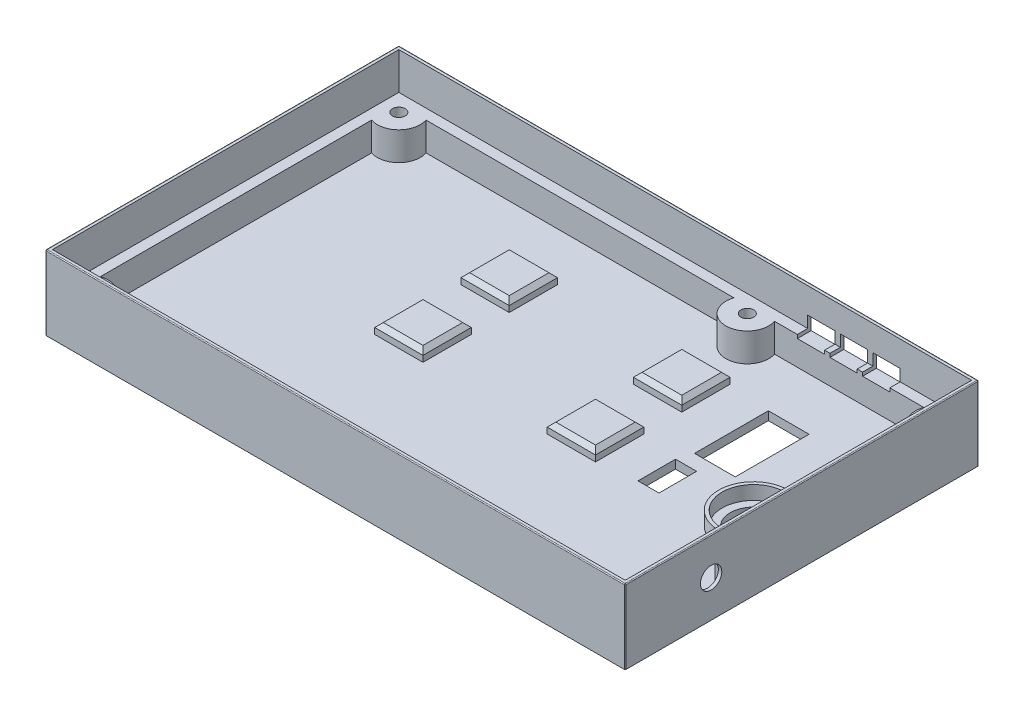
SolidWorks part; units mm, degrees
ref_plane "Front Plane" through (0, 0, 0) normal (0, 0, 1) x (1, 0, 0)
ref_plane "Top Plane" through (0, 0, 0) normal (0, 1, 0) x (1, 0, 0)
ref_plane "Right Plane" through (0, 0, 0) normal (1, 0, 0) x (0, 0, -1)
sketch "BaseSketch1" plane through (0, 0, 0) normal (0, 1, 0) x (1, 0, 0)
  line L1 (0, 0) -> (168, 0)
  line L2 (0, 0) -> (0, 102.4)
  line L3 (0, 102.4) -> (168, 102.4)
  line L4 (168, 0) -> (168, 102.4)
  line L5 (126.2, 83.3) -> (138, 83.3)
  line L6 (126.2, 83.3) -> (126.2, 61.9)
  line L7 (126.2, 61.9) -> (138, 61.9)
  line L8 (138, 83.3) -> (138, 61.9)
  line L9 (124.9, 46.8) -> (131, 46.8)
  line L10 (124.9, 46.8) -> (124.9, 57.7)
  line L11 (124.9, 57.7) -> (131, 57.7)
  line L12 (131, 46.8) -> (131, 57.7)
  circle A0 centre (57, 77.4) radius 2
  circle A1 centre (107, 77.4) radius 2
  circle A2 centre (57, 52.4) radius 2
  circle A3 centre (107, 52.4) radius 2
  circle A4 centre (6, 96.4) radius 1.85
  circle A5 centre (6, 6) radius 1.85
  circle A6 centre (162, 6) radius 1.85
  circle A7 centre (162, 96.4) radius 1.85
  circle A8 centre (107, 96.4) radius 1.85
  dimension "D16" = 3.7
  dimension "D7" = 4
  dimension "D1" = 102.4
  dimension "D2" = 168
  dimension "D3" = 50
  dimension "D4" = 25
  dimension "D6" = 25
  dimension "D8" = 21.4
  dimension "D9" = 11.8
  dimension "D10" = 40.5
  dimension "D12" = 6.1
  dimension "D13" = 10.9
  dimension "D15" = 55.6
  dimension "D17" = 6
  dimension "D18" = 6
  dimension "D19" = 6
  dimension "D20" = 6
  dimension "D5" = 57
  dimension "D11" = 41.8
  dimension "D14" = 43.1
  dimension "D21" = 107
extrude "BaseBoss-Extrude1" add sketch "BaseSketch1" along normal blind 2.5
sketch "Sketch2" plane through (0, 2.5, 0) normal (0, 1, 0) x (1, 0, 0)
  line L1 (0, 0) -> (168, 0)
  line L2 (0, 0) -> (0, 102.4)
  line L3 (0, 102.4) -> (168, 102.4)
  line L4 (168, 0) -> (168, 102.4)
  line L5 (4, 98.4) -> (164, 98.4)
  line L6 (4, 98.4) -> (4, 4)
  line L7 (4, 4) -> (164, 4)
  line L8 (164, 98.4) -> (164, 4)
  dimension "D1" = 4
  dimension "D2" = 4
  dimension "D3" = 4
  dimension "D4" = 4
extrude "WallBoss-Extrude2" add sketch "Sketch2" along normal blind 19
sketch "Sketch3" plane through (0, 2.5, 0) normal (0, 1, 0) x (1, 0, 0)
  line L1 (50, 84.4) -> (64, 84.4)
  line L2 (50, 84.4) -> (50, 70.4)
  line L3 (50, 70.4) -> (64, 70.4)
  line L4 (64, 84.4) -> (64, 70.4)
  line L5 (50, 84.4) -> (64, 70.4) construction
  line L6 (50, 70.4) -> (64, 84.4) construction
  line L7 (50, 59.4) -> (64, 59.4)
  line L8 (50, 59.4) -> (50, 45.4)
  line L9 (50, 45.4) -> (64, 45.4)
  line L10 (64, 59.4) -> (64, 45.4)
  line L11 (50, 59.4) -> (64, 45.4) construction
  line L12 (50, 45.4) -> (64, 59.4) construction
  line L13 (100, 84.4) -> (114, 84.4)
  line L14 (100, 84.4) -> (100, 70.4)
  line L15 (100, 70.4) -> (114, 70.4)
  line L16 (114, 84.4) -> (114, 70.4)
  line L17 (100, 84.4) -> (114, 70.4) construction
  line L18 (100, 70.4) -> (114, 84.4) construction
  line L19 (100, 59.4) -> (114, 59.4)
  line L20 (100, 59.4) -> (100, 45.4)
  line L21 (100, 45.4) -> (114, 45.4)
  line L22 (114, 59.4) -> (114, 45.4)
  line L23 (100, 59.4) -> (114, 45.4) construction
  line L24 (100, 45.4) -> (114, 59.4) construction
  point P0 (57, 77.4)
  point P6 (57, 52.4)
  point P12 (107, 77.4)
  point P18 (107, 52.4)
  dimension "D1" = 14
extrude "MountHoleBoss-Extrude3" add sketch "Sketch3" along normal blind 3
chamfer "MountHoleBossChamfer3" distance 1.25 angle 45 16 edges at (57, 5.5, -59.4) (107, 5.5, -59.4) (107, 5.5, -84.4) (57, 5.5, -84.4) (50, 5.5, -52.4) (100, 5.5, -52.4) (100, 5.5, -77.4) (50, 5.5, -77.4) (64, 5.5, -52.4) (114, 5.5, -52.4) (114, 5.5, -77.4) (64, 5.5, -77.4) (57, 5.5, -70.4) (57, 5.5, -45.4) (107, 5.5, -45.4) (107, 5.5, -70.4)
sketch "HDMI7MountHolesSketch8" plane through (0, 2.5, 0) normal (0, 1, 0) x (1, 0, 0)
  line L0 (164, 98.4) -> (4, 98.4) construction
  line L1 (4, 98.4) -> (4, 4) construction
  line L2 (4, 90.5243) -> (4, 98.4)
  line L3 (4, 98.4) -> (11.8757, 98.4)
  line L4 (164, 4) -> (164, 98.4) construction
  line L5 (4, 4) -> (164, 4) construction
  line L6 (4, 98.4) -> (4, 4) construction
  line L7 (4, 4) -> (164, 4) construction
  line L8 (156.1243, 98.4) -> (164, 98.4)
  line L9 (164, 98.4) -> (164, 90.5243)
  line L10 (156.1243, 4) -> (164, 4)
  line L11 (164, 4) -> (164, 11.8757)
  line L12 (11.8757, 4) -> (4, 4)
  line L13 (4, 4) -> (4, 11.8757)
  line L14 (101.1243, 98.4) -> (112.8757, 98.4)
  arc A0 (11.8757, 98.4) -> (4, 90.5243) centre (6, 96.4) cw
  circle A1 centre (6, 96.4) radius 1.85
  circle A2 centre (6, 96.4) radius 1.85 construction
  circle A3 centre (162, 96.4) radius 1.85
  circle A4 centre (162, 96.4) radius 1.85 construction
  arc A5 (164, 90.5243) -> (156.1243, 98.4) centre (162, 96.4) cw
  arc A6 (164, 11.8757) -> (156.1243, 4) centre (162, 6) ccw
  arc A7 (4, 11.8757) -> (11.8757, 4) centre (6, 6) cw
  circle A8 centre (162, 6) radius 1.85
  circle A9 centre (162, 6) radius 1.85 construction
  circle A10 centre (6, 6) radius 1.85
  circle A11 centre (6, 6) radius 1.85 construction
  arc A12 (101.1243, 98.4) -> (112.8757, 98.4) centre (107, 96.4) ccw
  circle A13 centre (107, 96.4) radius 1.85
  circle A14 centre (107, 96.4) radius 1.85 construction
extrude "HDMI7MountHolesBoss-Extrude4" add sketch "HDMI7MountHolesSketch8" along normal blind 8.25
sketch "DisplayButtonsSketch9" plane through (0, 0, -102.4) normal (0, 0, -1) x (-1, 0, 0)
  line L0 (-168, 21.5) -> (0, 21.5) construction
  line L1 (-146.3, 14.11) -> (-138.4, 14.11)
  line L2 (-146.3, 14.11) -> (-146.3, 9.71)
  line L3 (-146.3, 9.71) -> (-138.4, 9.71)
  line L4 (-138.4, 14.11) -> (-138.4, 9.71)
  line L5 (-136.85, 14.11) -> (-128.95, 14.11)
  line L6 (-136.85, 14.11) -> (-136.85, 9.71)
  line L7 (-136.85, 9.71) -> (-128.95, 9.71)
  line L8 (-128.95, 14.11) -> (-128.95, 9.71)
  line L9 (-127.4, 14.11) -> (-119.5, 14.11)
  line L10 (-127.4, 14.11) -> (-127.4, 9.71)
  line L11 (-127.4, 9.71) -> (-119.5, 9.71)
  line L12 (-119.5, 14.11) -> (-119.5, 9.71)
  line L13 (-168, 21.5) -> (-168, 0) construction
  dimension "D1" = 7.9
  dimension "D3" = 11.79
  dimension "D4" = 29.6
  dimension "D2" = 4.4
  dimension "D6" = 1.55
  dimension "D5" = 1.55
  dimension "D7" = 48.5
  dimension "D8" = 7.9
  dimension "D9" = 7.9
extrude "DisplayButtonsCut-Extrude1" cut sketch "DisplayButtonsSketch9" against normal up to next
sketch "AudioConnectorSketch10" plane through (168, 0, 0) normal (1, 0, 0) x (0, 0, -1)
  line L0 (0, 21.5) -> (102.4, 21.5) construction
  line L1 (0, 21.5) -> (0, 0) construction
  circle A0 centre (24.9, 10.7) radius 3.1
  dimension "D1" = 6.2
  dimension "D2" = 10.8
  dimension "D3" = 24.9
extrude "AudioConnectorCut-Extrude2" cut sketch "AudioConnectorSketch10" against normal up to next
sketch "M3BoreSketch11" plane through (0, 0, 0) normal (0, -1, 0) x (1, 0, 0)
  circle A0 centre (6, -6) radius 2.85
  circle A1 centre (162, -6) radius 2.85
  circle A2 centre (162, -96.4) radius 2.85
  circle A3 centre (6, -96.4) radius 2.85
  circle A4 centre (107, -96.4) radius 2.85
  dimension "D1" = 5.7
extrude "M3BoreCut-Extrude3" cut sketch "M3BoreSketch11" against normal blind 3
sketch "UpperThinWallSketch4" plane through (0, 21.5, 0) normal (0, 1, 0) x (1, 0, 0)
  line L1 (4, 98.4) -> (164, 98.4)
  line L2 (4, 98.4) -> (4, 4)
  line L3 (4, 4) -> (164, 4)
  line L4 (164, 98.4) -> (164, 4)
  line L6 (167, 1) -> (1, 1)
  line L7 (167, 1) -> (167, 101.4)
  line L8 (167, 101.4) -> (1, 101.4)
  line L9 (1, 1) -> (1, 101.4)
  dimension "D1" = 3
  dimension "D2" = 3
  dimension "D3" = 3
  dimension "D4" = 3
extrude "UpperThinWallCut-Extrude1" cut sketch "UpperThinWallSketch4" against normal blind 10.75
sketch "HDMI7AudioConnectorKnotchSketch5" plane through (0, 10.75, 0) normal (0, 1, 0) x (1, 0, 0)
  line L0 (164, 27.9996) -> (167, 27.9996) construction
  line L1 (164, 29.9996) -> (167, 29.9996)
  line L2 (164, 29.9996) -> (164, 19.8004)
  line L3 (164, 19.8004) -> (167, 19.8004)
  line L4 (167, 29.9996) -> (167, 19.8004)
  line L6 (167, 1) -> (167, 21.8004) construction
  line L7 (164, 11.8757) -> (164, 90.5243) construction
  line L8 (167, 21.8004) -> (164, 21.8004) construction
  dimension "D1" = 2
  dimension "D2" = 2
extrude "HDMI7AudioConnectorKnotchCut-Extrude2" cut sketch "HDMI7AudioConnectorKnotchSketch5" against normal blind 8.2
fillet "TopFillet1" radius 0.25 4 edges at (168, 21.5, -51.2) (84, 21.5, 0) (0, 21.5, -51.2) (84, 21.5, -102.4)
fillet "CornerFillet2" radius 0.25 8 edges at (0.0732, 21.4268, -0.0732) (0.0732, 21.4268, -102.3268) (167.9268, 21.4268, -0.0732) (0, 10.625, 0) (0, 10.625, -102.4) (168, 10.625, 0) (167.9268, 21.4268, -102.3268) (168, 10.625, -102.4)
sketch "SpeakerHoleSketch4" plane through (0, 2.5, 0) normal (0, 1, 0) x (1, 0, 0)
  line L0 (0.25, 102.4) -> (167.75, 102.4) construction
  line L1 (168, 102.15) -> (168, 0.25) construction
  circle A0 centre (153, 52.2) radius 6.75
  dimension "D1" = 13.5
  dimension "D2" = 50.2
  dimension "D3" = 15
extrude "SpeaerHoleCut-Extrude1" cut sketch "SpeakerHoleSketch4" against normal through all
sketch "SpeakerHolderSketch5" plane through (0, 2.5, 0) normal (0, 1, 0) x (1, 0, 0)
  line L2 (50, 59.4) -> (50, 45.4) construction
  line L3 (50, 45.4) -> (64, 45.4) construction
  circle A0 centre (153, 52.2) radius 9.1
  circle A1 centre (153, 52.2) radius 10.1
  dimension "D1" = 18.2
  dimension "D2" = 20.2
extrude "SpeakerHolderBoss-Extrude1" add sketch "SpeakerHolderSketch5" along normal blind 4
equation "\"HDMI7CaseWidth\"= 100mm + .4mm'Spec Add .4mm as width was slightly to tight"
equation "\"D1@BaseSketch1\" = \"HDMI7CaseWidth\" + \"HDMI7OuterCaseWallThickness\" * 2"
equation "\"HDMI7CaseLength\"= 165mm + 1mm'Spec Add 1mm as length did not fit"
equation "\"HDMI7CaseHeight\"= 21.5mm"
equation "\"HDMI7Height\"= 10.75mm'Spec"
equation "\"HDMI7MountingHoleOffset\"= 5mm'Spec"
equation "\"M3ScrewDiameter\"= 3mm + .5'Spec Add .5mm for easy screw insert"
equation "\"D2@BaseSketch1\"= \"HDMI7CaseLength\" + \"HDMI7OuterCaseWallThickness\" * 2"
equation "\"HDMI7BaseThickness\"= 2.5mm"
equation "\"HDMIMountHoleXDistance\"=50"
equation "\"D3@BaseSketch1\"=\"HDMIMountHoleXDistance\""
equation "\"HDMIMountHoleYDistance\"=25"
equation "\"D10@BaseSketch1\"=\"HDMI7HDMIConnectorDistanceFromTop\" + \"HDMI7OuterCaseWallThickness\" + \"HDMI7SpaceAroundAConnector\""
equation "\"D6@BaseSketch1\" = \"HDMI7MountingBracketOffsetFromTop\" + \"HDMI7OuterCaseWallThickness\""
equation "\"D15@BaseSketch1\"=\"HDMI7USBCConnectorDistanceFromTop\" + \"HDMI7OuterCaseWallThickness\" + \"HDMI7SpaceAroundAConnector\"*2"
equation "\"D1@BaseBoss-Extrude1\" = \"HDMI7BaseThickness\""
equation "\"D1@Sketch2\"=\"HDMI7OuterCaseWallThickness\" + \"HDMI7InnerCaseWallThickness\""
equation "\"D2@Sketch2\"=\"HDMI7OuterCaseWallThickness\" + \"HDMI7InnerCaseWallThickness\""
equation "\"D3@Sketch2\"=\"HDMI7OuterCaseWallThickness\" +\"HDMI7InnerCaseWallThickness\""
equation "\"D4@Sketch2\"=\"HDMI7OuterCaseWallThickness\" + \"HDMI7InnerCaseWallThickness\""
equation "\"D1@WallBoss-Extrude2\" = \"HDMI7CaseHeight\" - \"HDMI7BaseThickness\""
equation "\"D1@Sketch3\"=\"M3ScrewDiameter\"*4"
equation "\"D1@MountHoleBoss-Extrude3\"=\"M3ButtonHeadLength\""
equation "\"D16@BaseSketch1\"=\"M3ScrewDiameter\" +.2"
equation "\"D18@BaseSketch1\"=\"HDMI7MountingHoleOffset\" + \"HDMI7OuterCaseWallThickness\""
equation "\"D17@BaseSketch1\"=\"HDMI7MountingHoleOffset\"+\"HDMI7OuterCaseWallThickness\""
equation "\"D19@BaseSketch1\"=\"HDMI7MountingHoleOffset\"+\"HDMI7OuterCaseWallThickness\""
equation "\"D20@BaseSketch1\"=\"HDMI7MountingHoleOffset\"+\"HDMI7OuterCaseWallThickness\""
equation "\"D1@HDMI7MountHolesBoss-Extrude4\"=\"HDMI7CaseHeight\" - \"HDMI7Height\" - \"HDMI7BaseThickness\""
equation "\"D5@BaseSketch1\" = \"HDMI7MountingBracketOffsetFromEdge\" + \"HDMI7OuterCaseWallThickness\""
equation "\"D4@DisplayButtonsSketch9\"=\"HDMI7DisplayButtonDistanceFromNearestEdge\" + \"HDMI7OuterCaseWallThickness\" + \"HDMI7SpaceAroundAConnector\""
equation "\"D2@AudioConnectorSketch10\"= \"HDMI7AudioConnectorDistanceFromTop\" - \"HDMI7AudioConnectorHoleDiameter\" / 2"
equation "\"D3@AudioConnectorSketch10\"= \"HDMI7AudioConnectorDistanceFromNearestEdge\" + \"HDMI7OuterCaseWallThickness\" - \"HDMI7AudioConnectorHoleDiameter\" / 2"
equation "\"M3ButtonHeadDiameter\"= 5.5mm'Spec"
equation "\"M3ButtonHeadLength\"= 3mm'Spec"
equation "\"D1@M3BoreSketch11\"=\"M3ButtonHeadDiameter\" + .2mm"
equation "\"D1@M3BoreCut-Extrude3\"=\"M3ButtonHeadLength\""
equation "\"HDMI7InnerCaseWallThickness\"= 3mm"
equation "\"HDMI7OuterCaseWallThickness\"= 1mm"
equation "\"D1@UpperThinWallSketch4\" = \"HDMI7InnerCaseWallThickness\""
equation "\"D2@UpperThinWallSketch4\" = \"HDMI7InnerCaseWallThickness\""
equation "\"D3@UpperThinWallSketch4\" = \"HDMI7InnerCaseWallThickness\""
equation "\"D4@UpperThinWallSketch4\" = \"HDMI7InnerCaseWallThickness\""
equation "\"D1@UpperThinWallCut-Extrude1\" = \"HDMI7Height\""
equation "\"HDMI7AudioConnectorHoleDiameter\"= 6mm + \"HDMI7SpaceAroundAConnector\" * 2"
equation "\"D1@AudioConnectorSketch10\"=\"HDMI7AudioConnectorHoleDiameter\""
equation "\"HDMI7AudioConnectorDistanceFromNearestEdge\"= 27mm"
equation "\"HDMI7AudioConnectorDistanceFromTop\"= 13.8mm + \"HDMI7SpaceAroundAConnector\""
equation "\"D1@HDMI7AudioConnectorKnotchCut-Extrude2\"=\"HDMI7AudioConnectorHoleDiameter\" + 2mm"
equation "\"HDMI7DisplayButtonDistanceFromTop\"=11.69"
equation "\"D3@DisplayButtonsSketch9\"=\"HDMI7DisplayButtonDistanceFromTop\" + \"HDMI7SpaceAroundAConnector\""
equation "\"HDMI7DisplayButtonHeight\"= 4.2mm"
equation "\"D2@DisplayButtonsSketch9\"=\"HDMI7DisplayButtonHeight\" + \"HDMI7SpaceAroundAConnector\"*2"
equation "\"HDMI7DisplayButtonWidth\"= 7.7mm"
equation "\"D1@DisplayButtonsSketch9\"=\"HDMI7DisplayButtonWidth\" + \"HDMI7SpaceAroundAConnector\" * 2"
equation "\"HDMI7DisplayButtonDistanceFromNearestEdge\"= 28.5mm"
equation "\"HDMI7DisplayButtonOffsetBetweenEach\"=1.75"
equation "\"D6@DisplayButtonsSketch9\"=\"HDMI7DisplayButtonOffsetBetweenEach\" - \"HDMI7SpaceAroundAConnector\"*2"
equation "\"D5@DisplayButtonsSketch9\"=\"HDMI7DisplayButtonOffsetBetweenEach\" - \"HDMI7SpaceAroundAConnector\"*2"
equation "\"HDMI7HDMIConnectorLength\"= 21.2mm'Measured"
equation "\"D8@BaseSketch1\"=\"HDMI7HDMIConnectorLength\" + \"HDMI7SpaceAroundAConnector\"*2"
equation "\"HDMI7HDMIConnectorWidth\" = 11.6mm'Measured"
equation "\"D9@BaseSketch1\"=\"HDMI7HDMIConnectorWidth\" + \"HDMI7SpaceAroundAConnector\"*2"
equation "\"HDMI7USBCConnectorLength\"= 10.7mm'Measured"
equation "\"D13@BaseSketch1\"=\"HDMI7USBCConnectorLength\" + \"HDMI7SpaceAroundAConnector\"*2"
equation "\"HDMI7USBCConnectorWidth\" = 5.9mm'Measured"
equation "\"D12@BaseSketch1\"=\"HDMI7USBCConnectorWidth\" + \"HDMI7SpaceAroundAConnector\"*2"
equation "\"HDMI7HDMIConnectorDistanceFromNearestSide\"= 38.7mm"
equation "\"HDMI7USBCConnectorDistanceFromNearestSide\"= 40mm"
equation "\"D11@BaseSketch1\"=\"HDMI7HDMIConnectorDistanceFromNearestSide\" + \"HDMI7InnerCaseWallThickness\" + \"HDMI7SpaceAroundAConnector\""
equation "\"D14@BaseSketch1\"=\"HDMI7USBCConnectorDistanceFromNearestSide\" +\"HDMI7InnerCaseWallThickness\" + \"HDMI7SpaceAroundAConnector\""
equation "\"HDMI7USBCConnectorDistanceFromTop\"= 54.4mm"
equation "\"HDMI7HDMIConnectorDistanceFromTop\"= 39.4mm"
equation "\"HDMI7MountingBracketOffsetFromEdge\"= 56mm"
equation "\"HDMI7MountingBracketOffsetFromTop\"= 24mm"
equation "\"HDMI7SpaceAroundAConnector\"= .1mm"
equation "\"D7@BaseSketch1\"= \"M3HeatInsertHoleDiameter\""
equation "\"D8@DisplayButtonsSketch9\"=\"HDMI7DisplayButtonWidth\" + \"HDMI7SpaceAroundAConnector\"*2"
equation "\"D9@DisplayButtonsSketch9\"=\"HDMI7DisplayButtonWidth\" + \"HDMI7SpaceAroundAConnector\"*2"
equation "\"HDMI7MidMouningHoleOffset\"= 107'Spec is 106.55 but not enough"
equation "\"M3HeatInsertHoleDiameter\"= 4mm'Spec"
equation "\"SpeakerHoleDiameter\"= 13.5mm"
equation "\"D2@SpeakerHoleSketch4\" = \"HDMI7CaseWidth\" / 2"
equation "\"SpeakerDistanceFromNearestEdge\"= 15mm"
equation "\"D3@SpeakerHoleSketch4\" = \"SpeakerDistanceFromNearestEdge\""
equation "\"SpeakerDiameter\"= 18.2mm'Spec Add .2mm for Filament expansion"
equation "\"D1@SpeakerHolderSketch5\"=\"SpeakerDiameter\""
equation "\"D2@SpeakerHolderSketch5\"=\"SpeakerDiameter\" + 2mm"
equation "\"SpeakerDepth\"=4"
equation "\"D1@SpeakerHolderBoss-Extrude1\"=\"SpeakerDepth\""
equation "\"D21@BaseSketch1\"=\"HDMI7MidMouningHoleOffset\""
